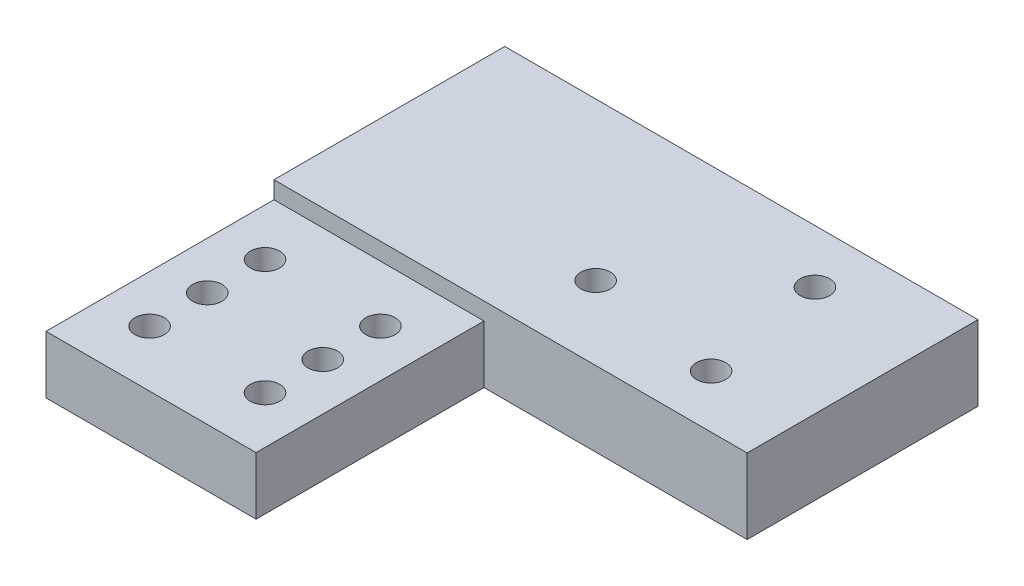
SolidWorks part; units mm, degrees
ref_plane "Front Plane" through (0, 0, 0) normal (0, 0, 1) x (1, 0, 0)
ref_plane "Top Plane" through (0, 0, 0) normal (0, 1, 0) x (1, 0, 0)
ref_plane "Right Plane" through (0, 0, 0) normal (1, 0, 0) x (0, 0, -1)
sketch "Sketch1" plane through (0, 0, 0) normal (0, 1, 0) x (1, 0, 0)
  line L1 (0, 0) -> (36.4, 0)
  line L2 (0, 0) -> (0, 39.5)
  line L3 (0, 39.5) -> (36.4, 39.5)
  line L4 (36.4, 0) -> (36.4, 39.5)
  circle A0 centre (8.2, 29.75) radius 2.55
  circle A1 centre (28.2, 29.75) radius 2.55
  circle A2 centre (28.2, 19.75) radius 2.55
  circle A3 centre (28.2, 9.75) radius 2.55
  circle A4 centre (8.2, 19.75) radius 2.55
  circle A5 centre (8.2, 9.75) radius 2.55
  dimension "D3" = 5.1
  dimension "D1" = 8.2
  dimension "D2" = 9.75
  dimension "D4" = 8.2
  dimension "D5" = 9.75
  dimension "D8" = 20
  dimension "D9" = 39.5
  dimension "D6" = 2
  dimension "D7" = 3
extrude "Boss-Extrude1" add sketch "Sketch1" along normal blind 10
sketch "Sketch2" plane through (0, 10, 0) normal (0, 1, 0) x (1, 0, 0)
  line L1 (0, 39.5) -> (82, 39.5)
  line L2 (0, 39.5) -> (0, 79.5)
  line L3 (0, 79.5) -> (82, 79.5)
  line L4 (82, 39.5) -> (82, 79.5)
  dimension "D1" = 82
  dimension "D2" = 40
extrude "Boss-Extrude2" add sketch "Sketch2" against normal blind 10 and the other way blind 3
sketch "Sketch4" plane through (0, 13, 0) normal (0, 1, 0) x (1, 0, 0)
  line L0 (66.5819, 48.6599) -> (66.5819, 39.5)
  line L2 (66.5819, 39.5) -> (82, 39.5)
  dimension "D1" = 9.1599
  dimension "D2" = 15.4181
  dimension "D3" = 0
  dimension "D4" = 0
  dimension "D5" = 15.4181
sketch "Sketch3" plane through (0, 13, 0) normal (0, 1, 0) x (1, 0, 0)
  line L7 (42.9961, 52.2457) -> (66.5819, 52.2457)
  line L8 (66.5819, 48.6599) -> (42.9961, 52.2457)
  line L9 (66.5819, 52.2457) -> (66.5819, 48.6599)
  line L10 (62.9961, 52.2457) -> (42.9961, 52.2457)
  line L11 (62.9961, 70.2457) -> (62.9961, 52.2457)
  line L12 (42.9961, 52.2457) -> (62.9961, 70.2457)
  dimension "D5" = 26.9072
  dimension "D1" = 18
  dimension "D2" = 3.5858
  dimension "D3" = 3.5858
  dimension "D4" = 23.5858
  dimension "D6" = 23.5858
  dimension "D7" = 23.8568
  dimension "D8" = 20
  dimension "D9" = 0
  dimension "D10" = 0
hole_wizard "Ø5.0mm Dowel Hole1" positions "3DSketch1" profile "Sketch5" hole size "Ø5.0" standard "ANSI Metric" end condition through all
sketch3d "3DSketch1"
  point P0 (42.9961, 13, -52.2457)
  point P3 (62.9961, 13, -70.2457)
  point P10 (66.5819, 13, -48.6599)
sketch "Sketch5" plane through (42.9961, 13, -52.2457) normal (1, 0, 0) x (0, 0, 1)
  line L0 (0, 0) -> (0, 13)
  line L1 (0, 13) -> (2.55, 13)
  line L2 (2.55, 13) -> (2.55, 0)
  line L5 (2.55, 0) -> (0, 0)
  line L11 (0, -6.35) -> (0, 107.95) construction
  dimension "Thru Hole Dia." = 5.1
  dimension "Thru Hole Depth" = 13
